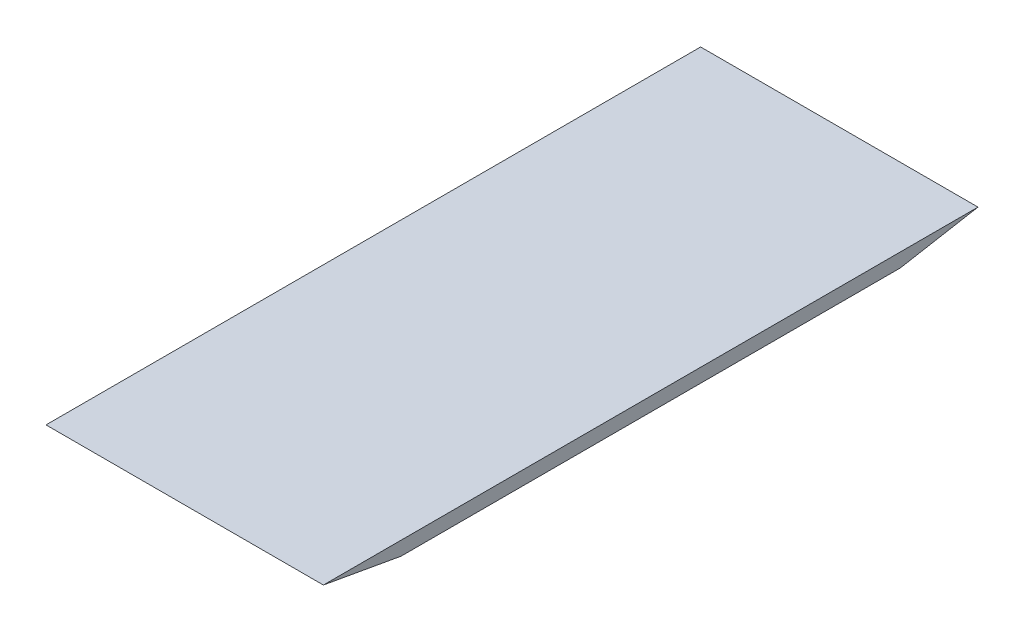
SolidWorks part; units mm, degrees
ref_plane "Front Plane" through (0, 0, 0) normal (0, 0, 1) x (1, 0, 0)
ref_plane "Top Plane" through (0, 0, 0) normal (0, 1, 0) x (1, 0, 0)
ref_plane "Right Plane" through (0, 0, 0) normal (1, 0, 0) x (0, 0, -1)
sketch "Sketch1" plane through (0, 0, 0) normal (1, 0, 0) x (0, 0, -1)
  line L0 (0, 0) -> (236, 0)
  line L1 (236, 0) -> (208, -5)
  line L2 (208, -5) -> (28, -5)
  line L3 (28, -5) -> (0, 0)
  point P3 (118, 0)
  dimension "D1" = 180
  dimension "D2" = 28
  dimension "D3" = 28
  dimension "D4" = 5
extrude "Boss-Extrude1" add sketch "Sketch1" along normal blind 100
